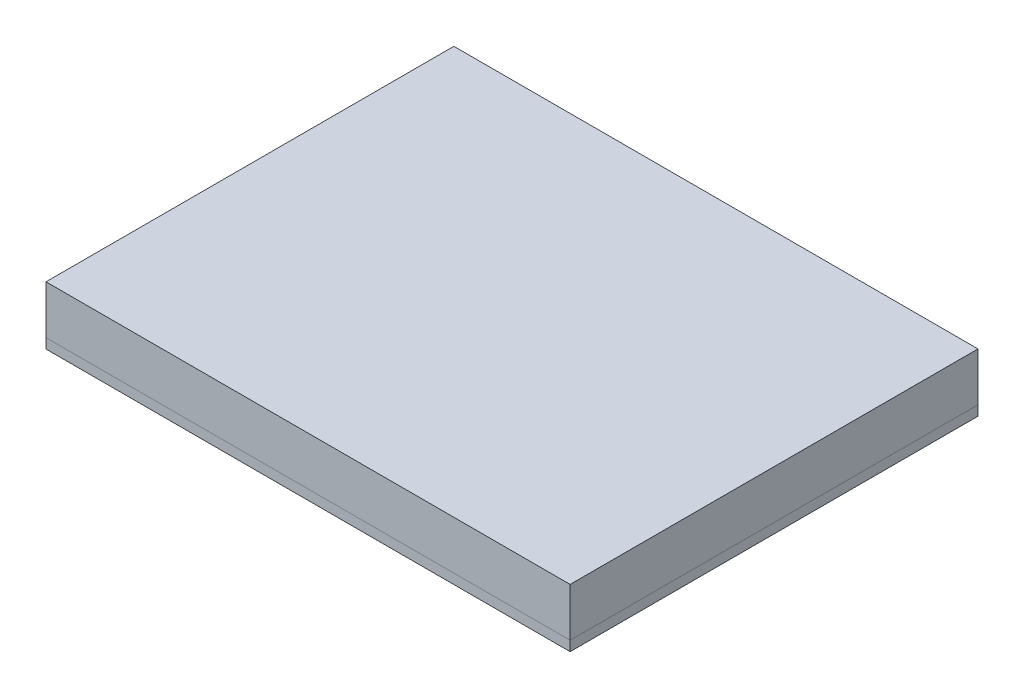
SolidWorks part; units mm, degrees
ref_plane "Front Plane" through (0, 0, 0) normal (0, 0, 1) x (1, 0, 0)
ref_plane "Top Plane" through (0, 0, 0) normal (0, 1, 0) x (1, 0, 0)
ref_plane "Right Plane" through (0, 0, 0) normal (1, 0, 0) x (0, 0, -1)
sketch "Sketch1" plane through (0, 0, 0) normal (0, 1, 0) x (1, 0, 0)
  line L1 (0, 0) -> (89.95, 0)
  line L2 (0, 0) -> (0, 70)
  line L3 (0, 70) -> (89.95, 70)
  line L4 (89.95, 0) -> (89.95, 70)
  dimension "D1" = 89.95
  dimension "D2" = 70
extrude "Boss-Extrude1" add sketch "Sketch1" along normal blind 1.7
extrude "Boss-Extrude2" add sketch "Sketch1<2>" along normal blind 8.3 from surface separate body starting at face at (44.975, 1.7, -35)
sketch "Sketch1<2>" plane through (0, 0, 0) normal (0, 1, 0) x (1, 0, 0) same geometry as "Sketch1"
